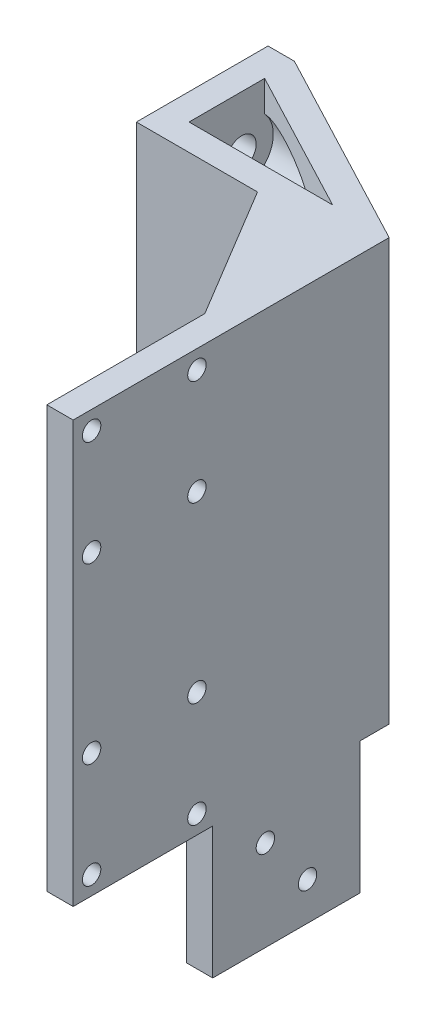
SolidWorks part; units mm, degrees
ref_plane "Plan de face" through (0, 0, 0) normal (0, 0, 1) x (1, 0, 0)
ref_plane "Plan de dessus" through (0, 0, 0) normal (0, 1, 0) x (1, 0, 0)
ref_plane "Plan de droite" through (0, 0, 0) normal (1, 0, 0) x (0, 0, -1)
sketch "Esquisse1" plane through (0, 0, 0) normal (0, 0, 1) x (1, 0, 0)
  line L1 (-33.3969, 24.3516) -> (9.6031, 24.3516)
  line L2 (-33.3969, 24.3516) -> (-33.3969, -55.6484)
  line L3 (-33.3969, -55.6484) -> (9.6031, -55.6484)
  line L4 (9.6031, 24.3516) -> (9.6031, -55.6484)
  dimension "D1" = 80
  dimension "D2" = 43
extrude "Boss.-Extru.1" add sketch "Esquisse1" along normal blind 5
sketch "Esquisse2" plane through (0, 0, 5) normal (0, 0, -1) x (-1, 0, 0)
  line L0 (-9.6031, 24.3516) -> (33.3969, 24.3516) construction
  line L1 (-9.6031, -55.6484) -> (-4.6031, -55.6484)
  line L2 (-9.6031, -55.6484) -> (-9.6031, 24.3516)
  line L3 (-9.6031, 24.3516) -> (-4.6031, 24.3516)
  line L4 (-4.6031, -55.6484) -> (-4.6031, 24.3516)
  dimension "D1" = 5
extrude "Boss.-Extru.2" add sketch "Esquisse2" against normal blind 55
sketch "Esquisse3" plane through (9.6031, 0, 0) normal (1, 0, 0) x (0, 0, -1)
  line L0 (-36.5, -52.1484) -> (-56.5, -52.1484) construction
  line L1 (-56.5, -52.1484) -> (-56.5, -32.1484) construction
  line L2 (-56.5, 20.8516) -> (-36.5, 20.8516) construction
  line L3 (-36.5, 20.8516) -> (-36.5, 0.8516) construction
  line L4 (-60, 24.3516) -> (-60, -55.6484) construction
  line L5 (-60, -55.6484) -> (0, -55.6484) construction
  line L6 (-60, 24.3516) -> (0, 24.3516) construction
  circle A0 centre (-56.5, -52.1484) radius 1.75
  circle A1 centre (-56.5, -32.1484) radius 1.75
  circle A2 centre (-36.5, -32.1484) radius 1.75
  circle A3 centre (-36.5, -52.1484) radius 1.75
  circle A4 centre (-56.5, 0.8516) radius 1.75
  circle A5 centre (-56.5, 20.8516) radius 1.75
  circle A6 centre (-36.5, 20.8516) radius 1.75
  circle A7 centre (-36.5, 0.8516) radius 1.75
  dimension "D1" = 3.5
  dimension "D2" = 20
  dimension "D3" = 3.5
  dimension "D4" = 3.5
  dimension "D5" = 3.5
extrude "Enlèv. mat.-Extru.1" cut sketch "Esquisse3" against normal up to next
sketch "Esquisse4" plane through (0, 0, 0) normal (0, 0, -1) x (-1, 0, 0)
  line L0 (-9.6031, 24.3516) -> (33.3969, 24.3516) construction
  line L1 (33.3969, -55.6484) -> (28.3969, -55.6484)
  line L2 (33.3969, -55.6484) -> (33.3969, 24.3516)
  line L3 (33.3969, 24.3516) -> (28.3969, 24.3516)
  line L4 (28.3969, -55.6484) -> (28.3969, 24.3516)
  dimension "D1" = 5
extrude "Boss.-Extru.3" add sketch "Esquisse4" along normal blind 20
sketch "Esquisse5" plane through (-28.3969, 0, 0) normal (1, 0, 0) x (0, 0, -1)
  line L0 (20, -55.6484) -> (0, -55.6484) construction
  line L1 (20, 24.3516) -> (0, 24.3516) construction
  circle A0 centre (10, 14.3516) radius 2.75
  circle A1 centre (10, -5.6484) radius 2.75
  circle A2 centre (10, -25.6484) radius 2.75
  circle A3 centre (10, -45.6484) radius 2.75
  point P12 (10, 24.3516)
  dimension "D1" = 5.5
  dimension "D2" = 10
  dimension "D3" = 10
  dimension "D4" = 20
  dimension "D5" = 20
extrude "Enlèv. mat.-Extru.2" cut sketch "Esquisse5" against normal up to next
sketch "Esquisse7" plane through (0, 24.3516, 0) normal (0, 1, 0) x (1, 0, 0)
  line L0 (9.6031, 0) -> (-28.3969, 20)
  line L1 (-28.3969, 20) -> (-28.3969, 14.3498)
  line L2 (-28.3969, 20) -> (-28.3969, 0) construction
  line L3 (-28.3969, 14.3498) -> (-1.1323, 0)
  line L4 (9.6031, 0) -> (-28.3969, 0) construction
  line L5 (-1.1323, 0) -> (9.6031, 0)
  dimension "D1" = 5
extrude "Boss.-Extru.4" add sketch "Esquisse7" against normal up to surface (80 mm away) up to face at (-11.8969, -55.6484, 11.25)
sketch "Esquisse8" plane through (-28.3969, 0, 0) normal (1, 0, 0) x (0, 0, -1)
  circle A0 centre (10, -45.6484) radius 6
  circle A1 centre (10, -25.6484) radius 6
  circle A2 centre (10, -5.6484) radius 6
  circle A3 centre (10, 14.3516) radius 6
  dimension "D1" = 12
extrude "Enlèv. mat.-Extru.4" cut sketch "Esquisse8" along normal up to next
chamfer "Chanfrein2" distance 25 distance2 15 1 edges at (4.6031, -15.6484, 5) first distance on face at (4.6031, 0.8516, 58.25)
sketch "Esquisse10" plane through (0, -55.6484, 0) normal (0, -1, 0) x (1, 0, 0)
  line L0 (9.6031, 60) -> (9.6031, 0) construction
  line L1 (9.6031, 33.5) -> (4.6031, 33.5)
  line L2 (9.6031, 33.5) -> (9.6031, 5.5)
  line L3 (9.6031, 5.5) -> (4.6031, 5.5)
  line L4 (4.6031, 33.5) -> (4.6031, 5.5)
  line L5 (9.6031, 60) -> (4.6031, 60) construction
  line L6 (4.6031, 60) -> (4.6031, 30) construction
  point P8 (9.6031, 5.5)
  point P9 (6.1381, 33.5)
  dimension "D1" = 28
  dimension "D2" = 26.5
extrude "Boss.-Extru.5" add sketch "Esquisse10" along normal blind 25
sketch "Esquisse11" plane through (4.6031, 0, 0) normal (-1, 0, 0) x (0, 0, 1)
  line L0 (15.5, -73.4293) -> (23.5, -73.4293) construction
  line L1 (23.5, -73.4293) -> (23.5, -63.4293) construction
  line L2 (33.5, -80.6484) -> (5.5, -80.6484) construction
  circle A0 centre (15.5, -73.4293) radius 1.75
  circle A1 centre (23.5, -63.4293) radius 1.75
  point P7 (19.5, -80.6484)
  point P8 (19.5, -73.4293)
  dimension "D1" = 3.5
  dimension "D2" = 10
  dimension "D3" = 8
extrude "Enlèv. mat.-Extru.5" cut sketch "Esquisse11" against normal up to next
